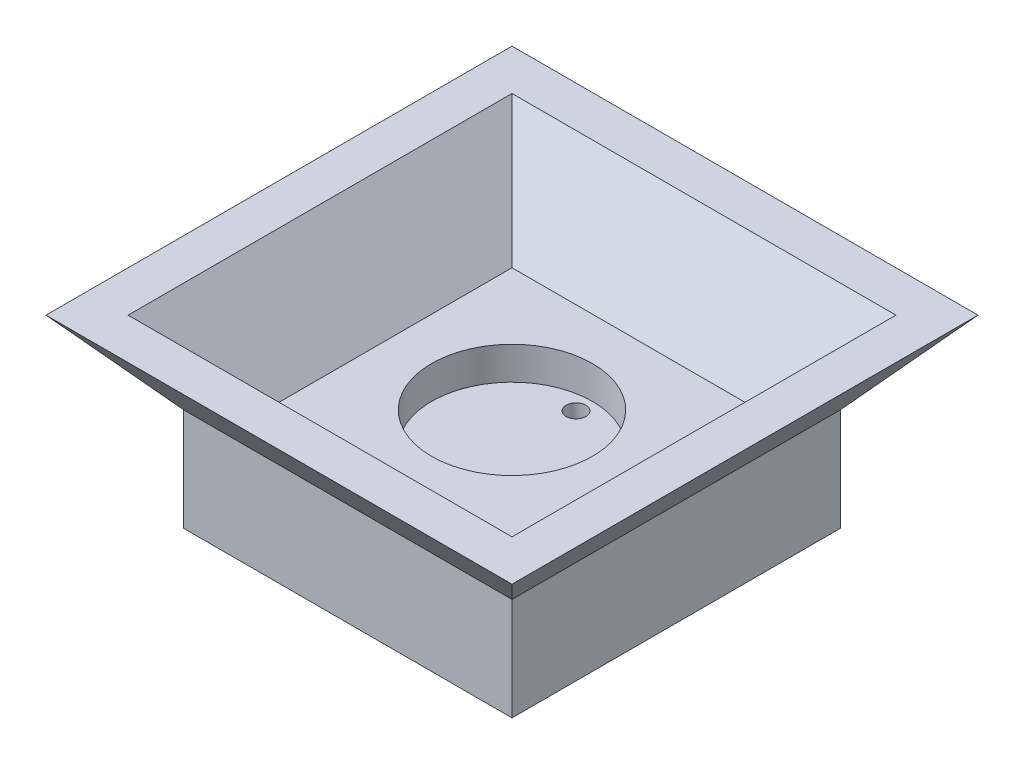
SolidWorks part; units mm, degrees
ref_plane "Front Plane" through (0, 0, 0) normal (0, 0, 1) x (1, 0, 0)
ref_plane "Top Plane" through (0, 0, 0) normal (0, 1, 0) x (1, 0, 0)
ref_plane "Right Plane" through (0, 0, 0) normal (1, 0, 0) x (0, 0, -1)
sketch "Sketch1" plane through (0, 0, 0) normal (0, 1, 0) x (1, 0, 0)
  line L1 (-25.4, -25.4) -> (25.4, -25.4)
  line L2 (-25.4, -25.4) -> (-25.4, 25.4)
  line L3 (-25.4, 25.4) -> (25.4, 25.4)
  line L4 (25.4, -25.4) -> (25.4, 25.4)
  line L5 (-25.4, -25.4) -> (25.4, 25.4) construction
  line L6 (-25.4, 25.4) -> (25.4, -25.4) construction
  point P0 (0, 0)
  dimension "D1" = 50.8
extrude "Boss-Extrude1" add sketch "Sketch1" along normal mid plane 31.75
sketch "Sketch2" plane through (0, 15.875, 0) normal (0, 1, 0) x (1, 0, 0)
  line L0 (-25.4, -25.4) -> (25.4, -25.4) construction
  line L1 (-25.4, 25.4) -> (25.4, 25.4)
  line L2 (-25.4, 25.4) -> (-25.4, -25.4)
  line L3 (-25.4, -25.4) -> (25.4, -25.4)
  line L4 (25.4, 25.4) -> (25.4, -25.4)
extrude "Boss-Extrude2" add sketch "Sketch2" along normal blind 12.7 draft 40 draft outward yes
mirror "Mirror1" about plane through (0, 0, 0) normal (0, 1, 0) of "Boss-Extrude2"
sketch "Sketch4" plane through (0, 28.575, 0) normal (0, 1, 0) x (1, 0, 0)
  line L0 (-29.7066, 25.4201) -> (-36.0566, 25.4201) construction
  line L1 (29.7066, -29.7066) -> (-29.7066, -29.7066)
  line L2 (29.7066, -29.7066) -> (29.7066, 29.7066)
  line L3 (29.7066, 29.7066) -> (-29.7066, 29.7066)
  line L4 (-29.7066, -29.7066) -> (-29.7066, 29.7066)
  line L5 (29.7066, -29.7066) -> (-29.7066, 29.7066) construction
  line L6 (29.7066, 29.7066) -> (-29.7066, -29.7066) construction
  line L7 (-36.0566, 36.0566) -> (-36.0566, -36.0566) construction
  point P0 (0, 0)
  dimension "D1" = 6.35
extrude "Cut-Extrude2" cut sketch "Sketch4" against normal blind 12.7 draft 40
sketch "Sketch5" plane through (0, 15.875, 0) normal (0, 1, 0) x (1, 0, 0)
  circle A0 centre (0, 0) radius 12.446
  dimension "D1" = 24.892
extrude "Cut-Extrude3" cut sketch "Sketch5" against normal blind 5.08
sketch "Sketch6" plane through (0, 10.795, 0) normal (0, 1, 0) x (1, 0, 0)
  line L1 (0, 12.446) -> (0, 7.366) construction
  line L2 (0, 7.366) -> (0, 12.446) construction
  circle A0 centre (0, 0) radius 12.446 construction
  circle A2 centre (0, 9.906) radius 1.524
  dimension "D2" = 3.048
  dimension "D1" = 5.08
extrude "Cut-Extrude4" cut sketch "Sketch6" against normal blind 20.32 contours A2
sketch "Sketch8" plane through (0, 0, 0) normal (0, 1, 0) x (1, 0, 0)
  line L1 (-52.018, 50.4034) -> (58.336, 50.4034)
  line L2 (-52.018, 50.4034) -> (-52.018, -56.5108)
  line L3 (-52.018, -56.5108) -> (58.336, -56.5108)
  line L4 (58.336, 50.4034) -> (58.336, -56.5108)
extrude "Cut-Extrude5" cut sketch "Sketch8" against normal up to next
